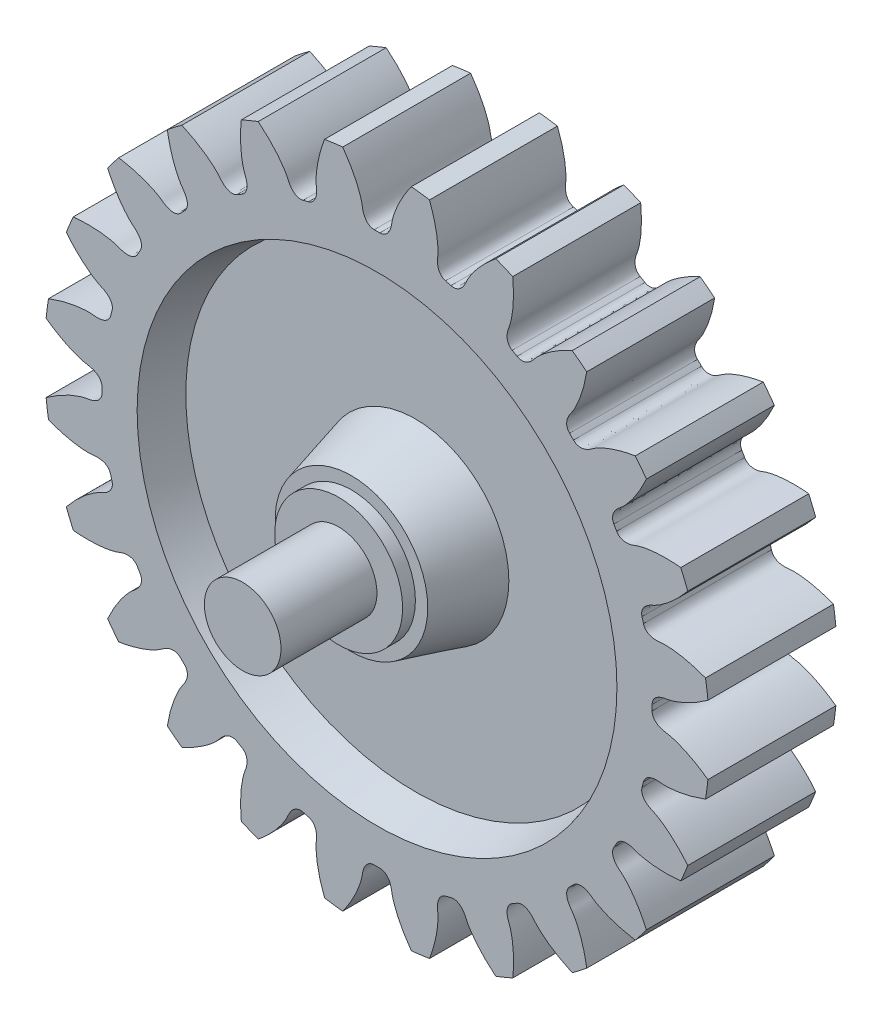
SolidWorks part; units mm, degrees
ref_plane "Front Plane" through (0, 0, 0) normal (0, 0, 1) x (1, 0, 0)
ref_plane "Top Plane" through (0, 0, 0) normal (0, 1, 0) x (1, 0, 0)
ref_plane "Right Plane" through (0, 0, 0) normal (1, 0, 0) x (0, 0, -1)
ref_axis "Axis1" through (0, 0, -88.99) along (0, 0, 1)
sketch "Gear-BaseSketch" plane through (0, 0, 0) normal (0, 0, 1) x (1, 0, 0)
  circle A0 centre (0, 0) radius 52
  dimension "D1" = 104
extrude "GearModule" add sketch "Gear-BaseSketch" along normal mid plane 20
sketch "Tooth-Sketch; Backlash: 0,0000mm" plane through (0, 0, 0) normal (0, 0, 1) x (1, 0, 0)
  line L0 (0, 0) -> (0, 67.6579) construction
  arc A0 (-5.4305, 51.8113) -> (5.4305, 51.8113) centre (0, 0) cw
  arc A1 (-0.4313, 42.9978) -> (0.4313, 42.9978) centre (0, 0) cw
  spline S0 degree 3 poles (-5.4305, 51.8113) (-5.0632, 51.3058) (-4.5579, 50.5556) (-3.9683, 49.5559) (-3.6029, 48.8781) (-3.2933, 48.2469) (-3.0353, 47.6654) (-2.8247, 47.1367) (-2.6568, 46.6634) (-2.5272, 46.2479) (-2.431, 45.8924) (-2.3637, 45.5988) (-2.3172, 45.3577) (-2.2916, 45.175) (-2.2673, 45.0318) (-2.2452, 44.9176) (-2.2051, 44.7342) (-2.1379, 44.4865) (-2.0249, 44.1806) (-1.8786, 43.8874) (-1.6839, 43.6026) (-1.4152, 43.3302) (-1.0028, 43.0725) (-0.6435, 42.9987) (-0.4313, 42.9978) knots 0 0 0 0 0.177934 0.257369 0.33045 0.397175 0.457545 0.511561 0.559222 0.600528 0.63548 0.664076 0.686318 0.705367 0.716617 0.72766 0.738509 0.77007 0.800665 0.831227 0.863172 0.898518 0.939478 1 1 1 1
  spline S1 degree 3 poles (5.4305, 51.8113) (5.0632, 51.3058) (4.5579, 50.5556) (3.9683, 49.5559) (3.6029, 48.8781) (3.2933, 48.2469) (3.0353, 47.6654) (2.8247, 47.1367) (2.6568, 46.6634) (2.5272, 46.2479) (2.431, 45.8924) (2.3637, 45.5988) (2.3172, 45.3577) (2.2916, 45.175) (2.2673, 45.0318) (2.2452, 44.9176) (2.2051, 44.7342) (2.1379, 44.4865) (2.0249, 44.1806) (1.8786, 43.8874) (1.6839, 43.6026) (1.4152, 43.3302) (1.0028, 43.0725) (0.6435, 42.9987) (0.4313, 42.9978) knots 0 0 0 0 0.177934 0.257369 0.33045 0.397175 0.457545 0.511561 0.559222 0.600528 0.63548 0.664076 0.686318 0.705367 0.716617 0.72766 0.738509 0.77007 0.800665 0.831227 0.863172 0.898518 0.939478 1 1 1 1
extrude "Tooth-Cut" cut sketch "Tooth-Sketch; Backlash: 0,0000mm" against normal through all and the other way through all
pattern_circular "Tooth Pattern, 24 / 24" count 24 every 15 about axis through (0, 0, -88.99) along (0, 0, 1) of "Tooth-Cut"
sketch "Sketch4" plane through (0, 0, 10) normal (0, 0, 1) x (1, 0, 0)
  circle A0 centre (0, 0) radius 37.5
  circle A1 centre (0, 0) radius 13
  point P5 (-22, 0)
  dimension "D1" = 75
  dimension "D2" = 26
  dimension "D3" = 0
extrude "Cut-Extrude2" cut sketch "Sketch4" against normal blind 6 draft 15
mirror "Mirror1" about plane through (0, 0, 0) normal (0, 0, 1) of "Cut-Extrude2"
sketch "Sketch8" plane through (0, 0, 10) normal (0, 0, 1) x (1, 0, 0)
  circle A0 centre (0, 0) radius 13
  point P3 (-22, 0)
  point P4 (0, 0)
  dimension "D1" = 26
extrude "Boss-Extrude3" add sketch "Sketch8" along normal blind 4 draft 15
mirror "Mirror3" about plane through (0, 0, 0) normal (0, 0, 1) of "Boss-Extrude3"
sketch "Sketch9" plane through (0, 0, 0) normal (0, 0, 1) x (1, 0, 0)
  line L1 (-2, 8.5) -> (2, 8.5)
  line L2 (-2, 8.5) -> (-2, 6.7082)
  line L4 (2, 8.5) -> (2, 6.7082)
  arc A0 (-2, 6.7082) -> (2, 6.7082) centre (0, 0) ccw
  dimension "D1" = 14
  dimension "D2" = 2
  dimension "D3" = 4
sketch "Sketch10" plane through (0, 0, 4) normal (0, 0, 1) x (1, 0, 0)
  circle A0 centre (0, 0) radius 10
  dimension "D1" = 20
extrude "Boss-Extrude5" add sketch "Sketch10" along normal blind 12
sketch "Sketch11" plane through (0, 0, 16) normal (0, 0, 1) x (1, 0, 0)
  circle A0 centre (0, 0) radius 5.99
  dimension "D1" = 11.98
extrude "Boss-Extrude6" add sketch "Sketch11" along normal blind 15
extrude "Cut-Extrude5" cut sketch "Sketch9" against normal mid plane 30
